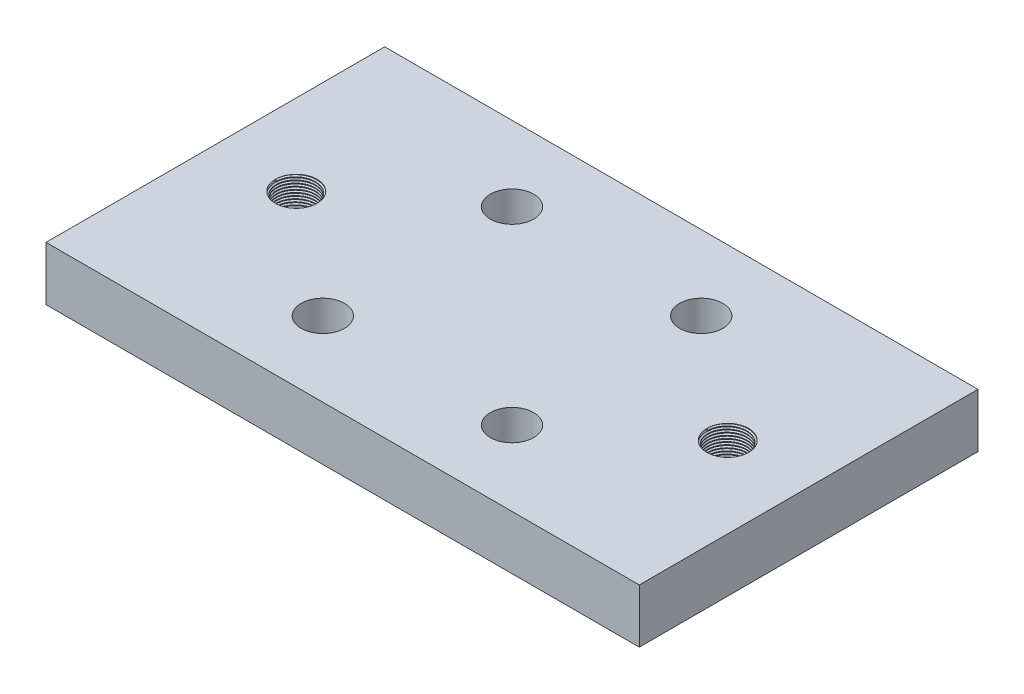
SolidWorks part; units mm, degrees
material "6061-T6 (SS)"
ref_plane "Front Plane" through (0, 0, 0) normal (0, 0, 1) x (1, 0, 0)
ref_plane "Top Plane" through (0, 0, 0) normal (0, 1, 0) x (1, 0, 0)
ref_plane "Right Plane" through (0, 0, 0) normal (1, 0, 0) x (0, 0, -1)
sketch "Sketch1" plane through (0, 0, 0) normal (0, 1, 0) x (1, 0, 0)
  line L6 (34.925, -19.939) -> (-34.925, -19.939)
  line L7 (-34.925, 6.9145) -> (-18.7017, 6.9145) construction
  line L8 (-34.925, 6.9145) -> (-34.925, -5.7855) construction
  line L9 (-34.925, -5.7855) -> (-19.0812, -5.7855) construction
  line L10 (34.925, 6.9145) -> (34.925, -5.7855) construction
  line L11 (18.7017, 6.9145) -> (34.925, 6.9145) construction
  line L12 (19.0812, -5.7855) -> (34.925, -5.7855) construction
  line L13 (34.925, -19.939) -> (34.925, 19.939)
  line L14 (34.925, 19.939) -> (-34.925, 19.939)
  line L15 (-34.925, -19.939) -> (-34.925, 19.939)
  line L16 (34.925, -19.939) -> (-34.925, 19.939) construction
  line L17 (34.925, 19.939) -> (-34.925, -19.939) construction
  arc A0 (-19.0812, -5.7855) -> (19.0812, -5.7855) centre (0, 0) ccw construction
  arc A1 (-19.0812, -5.7855) -> (19.0812, -5.7855) centre (0, 0) ccw construction
  arc A2 (18.7017, 6.9145) -> (-18.7017, 6.9145) centre (0, 0) ccw construction
  arc A3 (18.7017, 6.9145) -> (-18.7017, 6.9145) centre (0, 0) ccw construction
  point P19 (0, 0)
  dimension "D1" = 39.878
  dimension "D2" = 69.85
  dimension "D4" = 12.7
extrude "Boss-Extrude1" add sketch "Sketch1" along normal blind 6.35
hole_wizard "CSK for #10 Flat Head Machine Screw (100)1" positions "Sketch2" profile "Sketch4" countersink size "#10" standard "ANSI Inch" end condition through all
sketch "Sketch2" plane through (0, 0, 0) normal (0, -1, 0) x (-1, 0, 0)
  line L1 (-11.1369, 11.1369) -> (11.1369, 11.1369) construction
  line L2 (-11.1369, 11.1369) -> (-11.1369, -11.1369) construction
  line L3 (-11.1369, -11.1369) -> (11.1369, -11.1369) construction
  line L4 (11.1369, 11.1369) -> (11.1369, -11.1369) construction
  point P0 (-11.1369, 11.1369)
  point P3 (11.1369, 11.1369)
  point P6 (11.1369, -11.1369)
  point P9 (-11.1369, -11.1369)
sketch "Sketch4" plane through (11.1369, 0, -11.1369) normal (1, 0, 0) x (0, 0, -1)
  line L0 (0, 0) -> (0, 6.35)
  line L1 (0, 6.35) -> (2.5527, 6.35)
  line L2 (2.5527, 6.35) -> (2.5527, 1.9608)
  line L3 (2.5527, 1.9608) -> (4.8895, 0)
  line L5 (4.8895, 0) -> (0, 0)
  line L6 (-2.5527, 1.9608) -> (-4.8895, 0) construction
  line L11 (0, -6.35) -> (0, 107.95) construction
  dimension "Thru Hole Dia." = 5.1054
  dimension "Thru Hole Depth" = 6.35
  dimension "Near C'Sink Dia." = 9.779
  dimension "Near C'Sink Angle" = 100
hole_wizard "#10 (0.1935) Diameter Hole1" positions "Sketch7" profile "Sketch8" hole size "#10" standard "ANSI Inch" end condition through all
sketch "Sketch7" plane through (0, 0, 0) normal (0, -1, 0) x (-1, 0, 0)
  line L0 (0, 0) -> (-25.4, 0) construction
  point P0 (-25.4, 0)
  dimension "D1" = 25.4
sketch "Sketch8" plane through (25.4, 0, 0) normal (1, 0, 0) x (0, 0, -1)
  line L0 (0, 0) -> (0, 6.35)
  line L1 (0, 6.35) -> (2.4574, 6.35)
  line L2 (2.4574, 6.35) -> (2.4574, 0)
  line L5 (2.4574, 0) -> (0, 0)
  line L11 (0, -6.35) -> (0, 107.95) construction
  dimension "Thru Hole Dia." = 4.9149
  dimension "Thru Hole Depth" = 6.35
fillet "Fillet2" [suppressed] radius 6.35
mirror "Mirror1" about plane through (0, 0, 0) normal (1, 0, 0) of "#10 (0.1935) Diameter Hole1"
thread "Thread1" pitch 0.3175 method extrude profile "Thread Profile1" start angle 0, offset 0, length 6.35, pitch 0.3175, diameter 4.9149
ref_plane "Plane1" through (22.9426, 6.35, 0) normal (0, 0, 1) x (-1, 0, 0)
sketch "Thread Profile1" plane through (22.9426, 6.35, 0) normal (0, 0, 1) x (-1, 0, 0)
  line L0 (0, 0) -> (0, 0.3175) construction
  line L11 (0, 0) -> (0, 0.2778)
  line L12 (0, 0.2778) -> (-0.1719, 0.1786)
  line L13 (-0.1719, 0.1786) -> (-0.1719, 0.0992)
  line L15 (-0.1719, 0.0992) -> (0, 0)
  line L17 (-0.1719, 0.1389) -> (0, 0.1389) construction
  point P2 (0, 0)
  dimension "Pitch" = 0.3175
  dimension "Profile_Angle" = 60
  dimension "Profile_Land" = 0.0794
  dimension "Profile_Height" = 0.1719
thread "Thread2" pitch 0.3175 method extrude profile "Thread Profile2" start angle 0, offset 0, length 6.35, pitch 0.3175, diameter 4.9149
ref_plane "Plane2" through (-27.8575, 6.35, 0) normal (0, 0, 1) x (-1, 0, 0)
sketch "Thread Profile2" plane through (-27.8575, 6.35, 0) normal (0, 0, 1) x (-1, 0, 0)
  line L0 (0, 0) -> (0, 0.3175) construction
  line L11 (0, 0) -> (0, 0.2778)
  line L12 (0, 0.2778) -> (-0.1719, 0.1786)
  line L13 (-0.1719, 0.1786) -> (-0.1719, 0.0992)
  line L15 (-0.1719, 0.0992) -> (0, 0)
  line L17 (-0.1719, 0.1389) -> (0, 0.1389) construction
  point P2 (0, 0)
  dimension "Pitch" = 0.3175
  dimension "Profile_Angle" = 60
  dimension "Profile_Land" = 0.0794
  dimension "Profile_Height" = 0.1719
